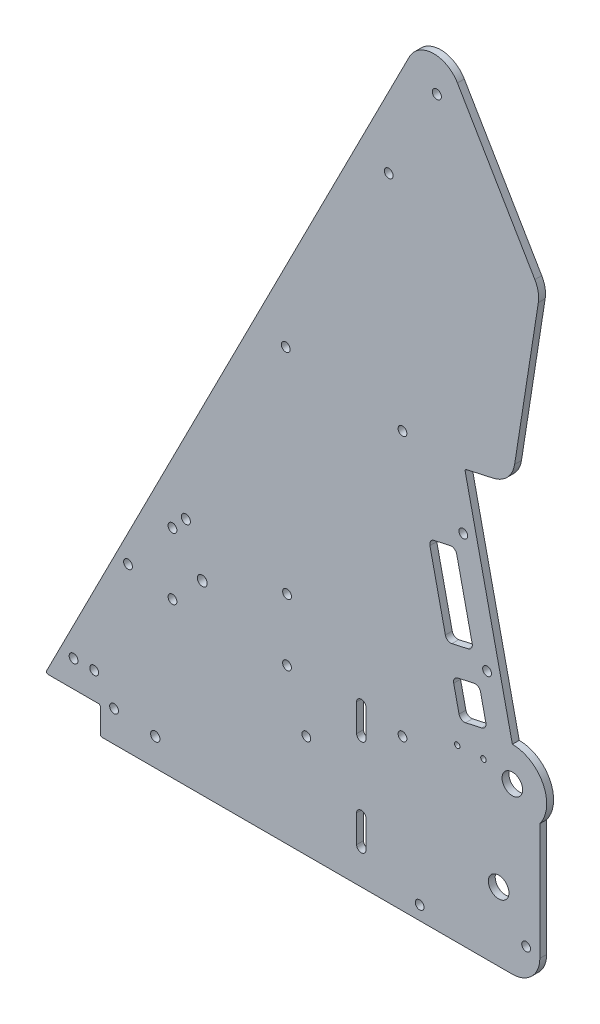
SolidWorks part; units mm, degrees
other "Markup1"
sketch "Sketch5"
ref_plane "Front Plane" through (0, 0, 0) normal (0, 0, 1) x (1, 0, 0)
ref_plane "Top Plane" through (0, 0, 0) normal (0, 1, 0) x (1, 0, 0)
ref_plane "Right Plane" through (0, 0, 0) normal (1, 0, 0) x (0, 0, -1)
sketch "Sketch1" plane through (0, 0, 0) normal (0, 0, 1) x (1, 0, 0)
  line L1 (228.6, -12.7) -> (228.6, 53.975)
  line L2 (178.7547, 351.4131) -> (0, 0)
  line L3 (228.6, 266.7) -> (178.7547, 351.4131)
  line L5 (0, 0) -> (25.4, 0)
  line L6 (25.4, 0) -> (25.4, -12.7)
  line L7 (25.4, -12.7) -> (228.6, -12.7)
  line L9 (215.9, 79.375) -> (193.9097, 178.5667)
  line L10 (193.9097, 178.5667) -> (215.6079, 183.377)
  line L11 (215.6079, 183.377) -> (228.6, 266.7)
  arc A0 (228.6, 53.975) -> (215.9, 79.375) centre (215.9, 63.5) ccw
  dimension "D7" = 12.7
  dimension "D8" = 76.2
  dimension "D10" = 31.75
  dimension "D2" = 279.4
  dimension "D3" = 25.4
  dimension "D4" = 215.9
  dimension "D5" = 394.2644
  dimension "D6" = 203.2
  dimension "D9" = 63.039
  dimension "D11" = 101.6
  dimension "D12" = 12.5
  dimension "D13" = 22.225
extrude "Boss-Extrude1" add sketch "Sketch1" along normal blind 3.175
sketch "Sketch2" plane through (0, 0, 3.175) normal (0, 0, 1) x (1, 0, 0)
  line L0 (178.7547, 351.4131) -> (0, 0) construction
  line L1 (25.4, -12.7) -> (228.6, -12.7) construction
  line L2 (215.9, 79.375) -> (193.9097, 178.5667) construction
  line L3 (193.9097, 178.5667) -> (215.6079, 183.377) construction
  line L4 (215.9, 79.375) -> (193.9097, 178.5667) construction
  line L5 (64.9432, 94.0578) -> (72.5445, 73.1732) construction
  line L6 (64.9432, 94.0578) -> (103.3734, 94.0578) construction
  line L10 (228.6, -12.7) -> (228.6, 53.975) construction
  circle A0 centre (64.9432, 94.0578) radius 2.0955
  circle A1 centre (180.975, 322.1643) radius 2.0955
  circle A2 centre (72.5445, 73.1732) radius 2.286
  circle A3 centre (193.2078, 152.3944) radius 2.032
  circle A4 centre (215.9, 63.5) radius 4.7625
  circle A7 centre (173.0375, -6.35) radius 2.032
  circle A8 centre (204.203, 102.7985) radius 2.032
  circle A26 centre (209.55, 19.05) radius 4.7625
  arc A30 (228.6, 53.975) -> (215.9, 79.375) centre (215.9, 63.5) ccw construction
  circle A31 centre (165.1, 179.3875) radius 2.032
  circle A35 centre (111.724, 87.4607) radius 2.032
  circle A36 centre (111.724, 58.8857) radius 2.032
  circle A37 centre (58.765, 58.8857) radius 2.032
  circle A38 centre (58.765, 87.4607) radius 2.032
  circle A39 centre (111.724, 58.8857) radius 1.905 construction
  circle A42 centre (111.724, 87.4607) radius 1.905 construction
  circle A43 centre (58.765, 58.8857) radius 1.905 construction
  circle A44 centre (58.765, 87.4607) radius 1.905 construction
  dimension "D3" = 4.191
  dimension "D5" = 4.191
  dimension "D9" = 4.572
  dimension "D20" = 9.525
  dimension "D23" = 9.525
  dimension "D18" = 4.064
  dimension "D26" = 4.064
  dimension "D14" = 4.064
  dimension "D10" = 4.064
  dimension "D2" = 15.24
  dimension "D6" = 15.24
  dimension "D7" = 22.225
  dimension "D21" = 44.45
  dimension "D22" = 6.35
  dimension "D19" = 160.3375
  dimension "D24" = 44.45
  dimension "D25" = 6.35
  dimension "D27" = 25.4
  dimension "D28" = 50.8
  dimension "D29" = 6.35
  dimension "D17" = 6.35
  dimension "D33" = 55.5625
  dimension "D15" = 114.3
  dimension "D4" = 180.975
  dimension "D8" = 70
extrude "Cut-Extrude1" cut sketch "Sketch2" against normal through all
sketch "Sketch7" plane through (0, 0, 3.175) normal (0, 0, 1) x (1, 0, 0)
  line L0 (146.05, 3.175) -> (146.05, 15.875) construction
  line L1 (143.891, 3.175) -> (143.891, 15.875)
  line L2 (148.209, 3.175) -> (148.209, 15.875)
  line L3 (146.05, 47.625) -> (146.05, 60.325) construction
  line L4 (143.891, 47.625) -> (143.891, 60.325)
  line L5 (148.209, 47.625) -> (148.209, 60.325)
  line L6 (25.4, -12.7) -> (228.6, -12.7) construction
  line L12 (228.6, -12.7) -> (228.6, 53.975) construction
  line L13 (25.4, -12.7) -> (228.6, -12.7) construction
  arc A0 (143.891, 3.175) -> (148.209, 3.175) centre (146.05, 3.175) ccw
  arc A1 (148.209, 15.875) -> (143.891, 15.875) centre (146.05, 15.875) ccw
  arc A2 (143.891, 47.625) -> (148.209, 47.625) centre (146.05, 47.625) ccw
  arc A3 (148.209, 60.325) -> (143.891, 60.325) centre (146.05, 60.325) ccw
  circle A8 centre (50.8, 0) radius 2.159
  point P2 (146.05, 9.525)
  point P9 (146.05, 53.975)
  dimension "D1" = 4.318
  dimension "D5" = 4.318
  dimension "D2" = 12.7
  dimension "D3" = 12.7
  dimension "D4" = 44.45
  dimension "D6" = 95.25
  dimension "D7" = 82.55
  dimension "D8" = 15.875
  dimension "D9" = 12.7
extrude "Cut-Extrude2" cut sketch "Sketch7" against normal through all
sketch "Sketch10" plane through (0, 0, 3.175) normal (0, 0, 1) x (1, 0, 0)
  circle A0 centre (120.65, 34.925) radius 2.032
  circle A1 centre (165.1, 57.15) radius 2.032
  circle A2 centre (13.0465, 12.3347) radius 2.032
  circle A3 centre (22.5715, 12.3347) radius 2.032
  circle A4 centre (38.2114, 62.6398) radius 2.032
  dimension "D1" = 4.064
  dimension "D3" = 34.925
  dimension "D2" = 120.65
  dimension "D4" = 63.5
  dimension "D5" = 69.85
extrude "Cut-Extrude3" cut sketch "Sketch10" against normal up to next
fillet "Fillet1" radius 12.7 4 edges at (228.6, -12.7, 1.5875) (178.7547, 351.4131, 1.5875) (215.6079, 183.377, 1.5875) (228.6, 266.7, 1.5875)
fillet "Fillet2" radius 0.7937 4 edges at (25.4, -12.7, 1.5875) (25.4, 0, 1.5875) (193.9097, 178.5667, 1.5875) (0, 0, 1.5875)
sketch "Sketch12" plane through (0, 0, 3.175) normal (0, 0, 1) x (1, 0, 0)
  circle A0 centre (31.75, 1.5875) radius 2.032
  circle A1 centre (173.0375, -6.35) radius 2.032
  circle A2 centre (222.25, 1.5875) radius 2.032
  dimension "D1" = 4.064
extrude "Cut-Extrude5" cut sketch "Sketch12" against normal through all
sketch "Sketch13" plane through (0, 0, 3.175) normal (0, 0, 1) x (1, 0, 0)
  line L1 (228.6, 0) -> (228.6, 53.975) construction
  line L2 (1.2943, 0) -> (24.6062, 0) construction
  line L3 (26.1937, -12.7) -> (215.9, -12.7) construction
  circle A0 centre (111.125, 186.055) radius 2.032
  circle A1 centre (158.75, 279.4) radius 2.032
  dimension "D2" = 4.064
  dimension "D5" = 4.064
  dimension "D1" = 198.755
  dimension "D3" = 69.85
  dimension "D4" = 279.4
  dimension "D6" = 117.475
extrude "Cut-Extrude6" cut sketch "Sketch13" against normal through all
sketch "Sketch14" plane through (0, 0, 3.175) normal (0, 0, 1) x (1, 0, 0)
  line L0 (177.2237, 142.3466) -> (189.6226, 145.0954)
  line L1 (189.6226, 145.0954) -> (197.869, 107.8985)
  line L2 (197.869, 107.8985) -> (185.47, 105.1497)
  line L3 (185.47, 105.1497) -> (177.2237, 142.3466)
  line L4 (189.6226, 145.0954) -> (177.2237, 142.3466) construction
  line L5 (188.2188, 92.7508) -> (200.6178, 95.4995)
  line L6 (188.2188, 92.7508) -> (191.7922, 76.6321)
  line L7 (191.7922, 76.6321) -> (204.1912, 79.3809)
  line L8 (200.6178, 95.4995) -> (204.1912, 79.3809)
  line L11 (197.869, 107.8985) -> (189.6226, 145.0954) construction
  line L12 (177.2237, 142.3466) -> (185.47, 105.1497) construction
  line L13 (185.47, 105.1497) -> (197.869, 107.8985) construction
  line L14 (204.1912, 79.3809) -> (200.6178, 95.4995) construction
  line L15 (191.7922, 76.6321) -> (204.1912, 79.3809) construction
  line L16 (188.2188, 92.7508) -> (191.7922, 76.6321) construction
  line L17 (200.6178, 95.4995) -> (188.2188, 92.7508) construction
  circle A0 centre (190.4268, 66.2609) radius 1.27
  circle A1 centre (202.5335, 66.7895) radius 1.27
  circle A2 centre (190.4268, 66.2609) radius 1.27 construction
  circle A3 centre (202.5335, 66.7895) radius 1.27 construction
  point P8 (152.4, 88.9)
extrude "Cut-Extrude7" cut sketch "Sketch14" against normal through all both and the other way through all
fillet "Fillet3" radius 2.54 8 edges at (200.6178, 95.4995, 1.5875) (188.2188, 92.7508, 1.5875) (191.7922, 76.6321, 1.5875) (204.1912, 79.3809, 1.5875) (197.869, 107.8985, 1.5875) (185.47, 105.1497, 1.5875) (177.2237, 142.3466, 1.5875) (189.6226, 145.0954, 1.5875)
equation "\"D6@Sketch2\"=\"D2@Sketch2\""
